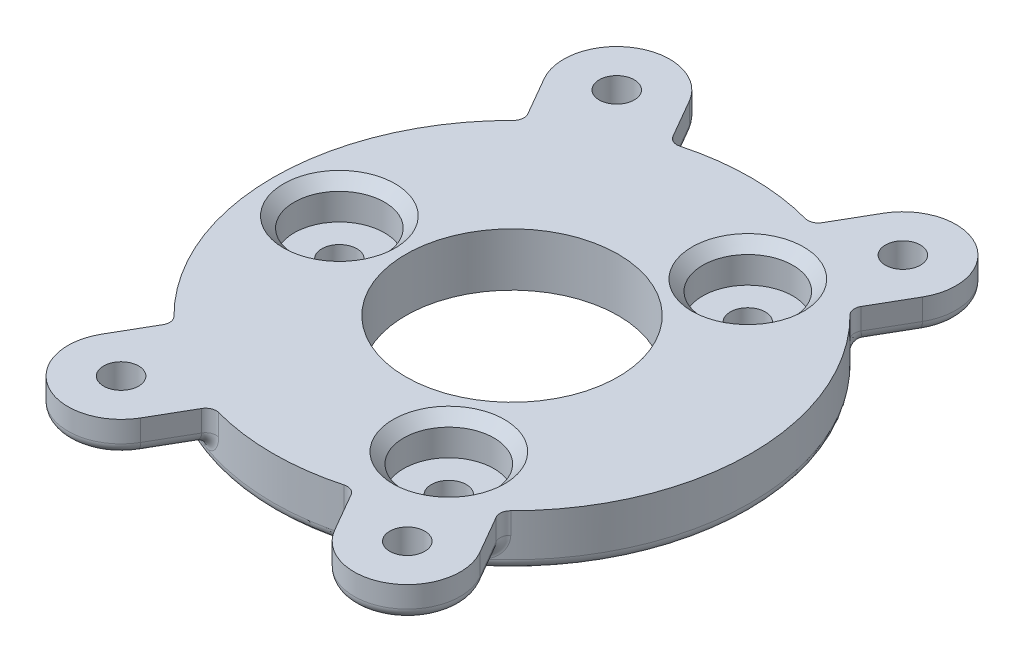
SolidWorks part; units mm, degrees
ref_plane "Front Plane" through (0, 0, 0) normal (0, 0, 1) x (1, 0, 0)
ref_plane "Top Plane" through (0, 0, 0) normal (0, 1, 0) x (1, 0, 0)
ref_plane "Right Plane" through (0, 0, 0) normal (1, 0, 0) x (0, 0, -1)
ref_plane "Plane1" through (0, 11, 0) normal (0, 1, 0) x (1, 0, 0)
sketch "Sketch8" plane through (0, 11, 0) normal (0, 1, 0) x (1, 0, 0)
  line L0 (0, 0) -> (0, 45) construction
  line L1 (0, 0) -> (-22.5, 38.9711) construction
  line L3 (-30.5977, 32.9967) -> (-35.5977, 41.657)
  line L4 (-13.2772, 42.9967) -> (-18.2772, 51.657)
  line L6 (0, -6.05) -> (0, 6.05) construction
  line L7 (13.2772, 42.9967) -> (18.2772, 51.657)
  line L8 (30.5977, 32.9967) -> (35.5977, 41.657)
  line L9 (-6.05, 0) -> (6.05, 0) construction
  line L10 (30.5977, -32.9967) -> (35.5977, -41.657)
  line L11 (13.2772, -42.9967) -> (18.2772, -51.657)
  line L12 (-13.2772, -42.9967) -> (-18.2772, -51.657)
  line L13 (-30.5977, -32.9967) -> (-35.5977, -41.657)
  circle A0 centre (0, 0) radius 45
  arc A1 (-18.2772, 51.657) -> (-35.5977, 41.657) centre (-26.9374, 46.657) ccw
  arc A2 (18.2772, 51.657) -> (35.5977, 41.657) centre (26.9374, 46.657) cw
  arc A3 (18.2772, -51.657) -> (35.5977, -41.657) centre (26.9374, -46.657) ccw
  arc A4 (-18.2772, -51.657) -> (-35.5977, -41.657) centre (-26.9374, -46.657) cw
  dimension "D1" = 90
  dimension "D2" = 30
  dimension "D3" = 10
  dimension "D4" = 20
extrude "Boss-Extrude4" add sketch "Sketch8" against normal blind 6 separate body contours A0 | L4 A1 L3 A0 | A2 L7 A0 L8 | L11 A3 L10 A0 | A4 L12 A0 L13
sketch "Sketch10" plane through (0, 5, 0) normal (0, -1, 0) x (1, 0, 0)
  circle A4 centre (0, 0) radius 45
extrude "Boss-Extrude5" add sketch "Sketch10" along normal blind 4
fillet "Fillet2" radius 2 24 edges at (31.9374, 5, 55.3172) (33.0977, 5, 37.3268) (33.0977, 5, -37.3268) (31.9374, 5, -55.3172) (-13.2772, 8, 42.9967) (-30.5977, 8, 32.9967) (-30.5977, 8, -32.9967) (-13.2772, 8, -42.9967) (13.2772, 8, -42.9967) (30.5977, 8, -32.9967) (30.5977, 8, 32.9967) (13.2772, 8, 42.9967) (15.7772, 5, -47.3268) (-15.7772, 5, -47.3268) (-31.9374, 5, -55.3172) (-33.0977, 5, -37.3268) (-22.5, 5, -38.9711) (-22.5, 5, 38.9711) (22.5, 5, 38.9711) (-33.0977, 5, 37.3268) (22.5, 5, -38.9711) (-31.9374, 5, 55.3172) (-15.7772, 5, 47.3268) (15.7772, 5, 47.3268)
hole_wizard "M6 Clearance Hole1" positions "Sketch14" profile "Sketch15" hole size "M6" standard "DIN" end condition through all
sketch "Sketch14" plane through (0, 11, 0) normal (0, 1, 0) x (1, 0, 0)
  point P0 (-26.9374, 46.657)
  point P3 (26.9374, 46.657)
  point P6 (-26.9374, -46.657)
  point P9 (26.9374, -46.657)
sketch "Sketch15" plane through (-26.9374, 11, -46.657) normal (1, 0, 0) x (0, 0, 1)
  line L0 (0, 0) -> (0, 10)
  line L1 (0, 10) -> (3.3, 10)
  line L2 (3.3, 10) -> (3.3, 0)
  line L5 (3.3, 0) -> (0, 0)
  line L11 (0, -6.35) -> (0, 107.95) construction
  dimension "Thru Hole Dia." = 6.6
  dimension "Thru Hole Depth" = 10
hole_wizard "CBORE for M6 Hex Head2" positions "Sketch17" profile "Sketch18" counterbore size "M6" standard "DIN" end condition up to next
sketch "Sketch17" plane through (0, 11, 0) normal (0, 1, 0) x (1, 0, 0)
  point P0 (-32.5, 0)
  point P4 (-14.9817, -28.8409)
  point P5 (-32.5, 0)
  dimension "D1" = 32.5
sketch "Sketch18" plane through (-32.5, 11, 0) normal (1, 0, 0) x (0, 0, 1)
  line L0 (0, 0) -> (0, 10.001)
  line L1 (0, 10.001) -> (3.3, 10.001)
  line L3 (3.3, 10.001) -> (3.3, 7)
  line L4 (3.3, 7) -> (8.5, 7)
  line L5 (8.5, 7) -> (8.5, 0)
  line L7 (8.5, 0) -> (0, 0)
  line L11 (0, -6.35) -> (0, 107.95) construction
  dimension "Thru Hole Dia." = 6.6
  dimension "Thru Hole Depth" = 10.001
  dimension "C'Bore Dia." = 17
  dimension "C'Bore Depth" = 7
pattern_circular "CirPattern1" count 3 over 360 about axis through (0, 0, 0) along (0, 1, 0) of "CBORE for M6 Hex Head2"
sketch "Sketch19" plane through (0, 11, 0) normal (0, 1, 0) x (1, 0, 0)
  circle A0 centre (0, 0) radius 20
extrude "Cut-Extrude1" cut sketch "Sketch19" against normal through all
fillet "Fillet3" radius 2 1 edges at (0, 1, -45)
chamfer "Chamfer1" distance 2 angle 45 3 edges at (16.25, 11, -19.6458) (16.25, 11, 36.6458) (-32.5, 11, 8.5)
